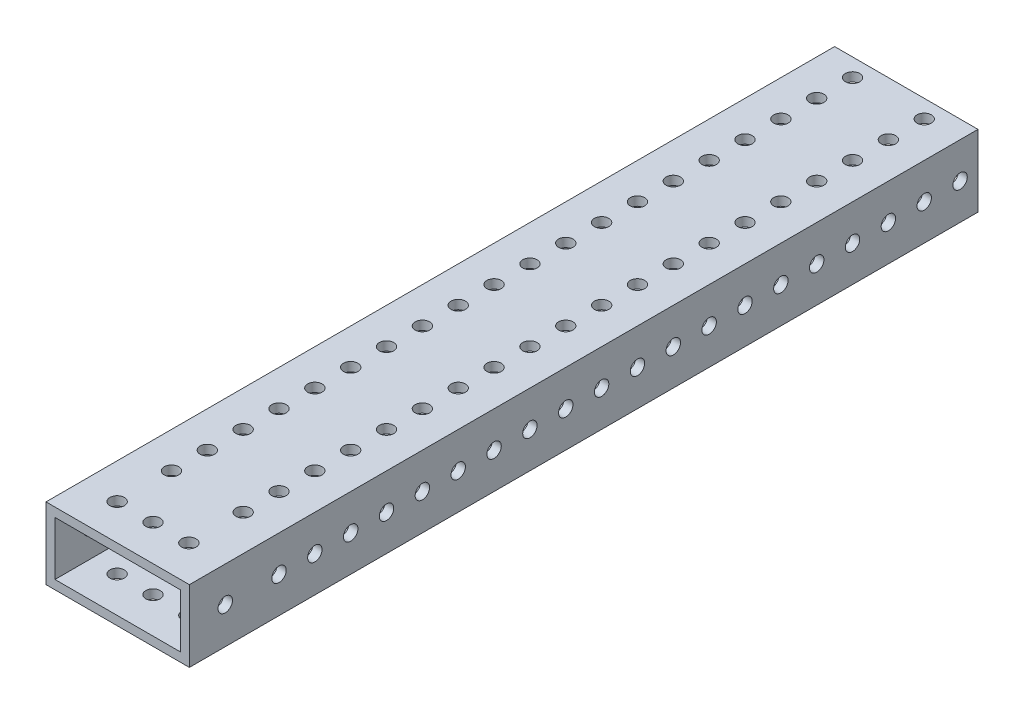
SolidWorks part; units mm, degrees
material "6061-T6 (SS)"
ref_plane "Front Plane" through (0, 0, 0) normal (0, 0, 1) x (1, 0, 0)
ref_plane "Top Plane" through (0, 0, 0) normal (0, 1, 0) x (1, 0, 0)
ref_plane "Right Plane" through (0, 0, 0) normal (1, 0, 0) x (0, 0, -1)
sketch "Sketch1" plane through (0, 0, 0) normal (0, 1, 0) x (1, 0, 0)
  line L1 (0, 0) -> (50.8, 0)
  line L2 (0, 0) -> (0, 279.4)
  line L3 (0, 279.4) -> (50.8, 279.4)
  line L4 (50.8, 0) -> (50.8, 279.4)
  dimension "D1" = 50.8
  dimension "D2" = 279.4
extrude "Boss-Extrude1" add sketch "Sketch1" along normal blind 25.4
sketch "Sketch2" plane through (0, 0, 0) normal (0, 0, 1) x (1, 0, 0)
  line L3 (3.175, 3.175) -> (47.625, 3.175)
  line L4 (3.175, 3.175) -> (3.175, 22.225)
  line L5 (3.175, 22.225) -> (47.625, 22.225)
  line L6 (47.625, 3.175) -> (47.625, 22.225)
  line L7 (0, 25.4) -> (0, 0) construction
  line L8 (50.8, 25.4) -> (50.8, 0) construction
  line L9 (0, 0) -> (50.8, 0) construction
  line L10 (0, 25.4) -> (50.8, 25.4) construction
  point P8 (25.4, 12.7)
  dimension "D1" = 3.175
  dimension "D2" = 3.175
  dimension "D3" = 3.175
  dimension "D4" = 3.175
extrude "Cut-Extrude1" cut sketch "Sketch2" against normal through all
sketch "Sketch4" plane through (0, 25.4, 0) normal (0, 1, 0) x (1, 0, 0)
  line L0 (0, 0) -> (50.8, 0) construction
  line L1 (0, 279.4) -> (0, 0) construction
  line L2 (50.8, 0) -> (50.8, 279.4) construction
  circle A0 centre (12.7, 6.35) radius 2.5527 construction
  circle A1 centre (38.1, 6.35) radius 2.5527 construction
  circle A2 centre (12.7, 19.05) radius 2.5527 construction
  circle A3 centre (38.1, 19.05) radius 2.5527 construction
  circle A4 centre (12.7, 31.75) radius 2.5527
  circle A5 centre (38.1, 31.75) radius 2.5527
  circle A6 centre (12.7, 44.45) radius 2.5527
  circle A7 centre (38.1, 44.45) radius 2.5527
  circle A8 centre (12.7, 57.15) radius 2.5527
  circle A9 centre (38.1, 57.15) radius 2.5527
  circle A10 centre (12.7, 69.85) radius 2.5527
  circle A11 centre (38.1, 69.85) radius 2.5527
  circle A12 centre (12.7, 82.55) radius 2.5527
  circle A13 centre (38.1, 82.55) radius 2.5527
  circle A14 centre (12.7, 95.25) radius 2.5527
  circle A15 centre (38.1, 95.25) radius 2.5527
  circle A16 centre (12.7, 107.95) radius 2.5527
  circle A17 centre (38.1, 107.95) radius 2.5527
  circle A18 centre (12.7, 120.65) radius 2.5527
  circle A19 centre (38.1, 120.65) radius 2.5527
  circle A20 centre (12.7, 133.35) radius 2.5527
  circle A21 centre (38.1, 133.35) radius 2.5527
  circle A22 centre (12.7, 146.05) radius 2.5527
  circle A23 centre (38.1, 146.05) radius 2.5527
  circle A24 centre (12.7, 158.75) radius 2.5527
  circle A25 centre (38.1, 158.75) radius 2.5527
  circle A26 centre (12.7, 171.45) radius 2.5527
  circle A27 centre (38.1, 171.45) radius 2.5527
  circle A28 centre (12.7, 184.15) radius 2.5527
  circle A29 centre (38.1, 184.15) radius 2.5527
  circle A30 centre (12.7, 196.85) radius 2.5527
  circle A31 centre (38.1, 196.85) radius 2.5527
  circle A32 centre (12.7, 209.55) radius 2.5527
  circle A33 centre (38.1, 209.55) radius 2.5527
  circle A34 centre (12.7, 222.25) radius 2.5527
  circle A35 centre (38.1, 222.25) radius 2.5527
  circle A36 centre (12.7, 234.95) radius 2.5527
  circle A37 centre (38.1, 234.95) radius 2.5527
  circle A38 centre (12.7, 247.65) radius 2.5527
  circle A39 centre (38.1, 247.65) radius 2.5527
  circle A40 centre (12.7, 260.35) radius 2.5527
  circle A41 centre (38.1, 260.35) radius 2.5527
  circle A42 centre (12.7, 273.05) radius 2.5527
  circle A43 centre (38.1, 273.05) radius 2.5527
  circle A44 centre (12.7, 285.75) radius 2.5527
  circle A45 centre (38.1, 285.75) radius 2.5527
  circle A46 centre (12.7, 298.45) radius 2.5527
  circle A47 centre (38.1, 298.45) radius 2.5527
  circle A48 centre (12.7, 311.15) radius 2.5527
  circle A49 centre (38.1, 311.15) radius 2.5527
  circle A50 centre (12.7, 323.85) radius 2.5527
  circle A51 centre (38.1, 323.85) radius 2.5527
  circle A52 centre (12.7, 336.55) radius 2.5527
  circle A53 centre (38.1, 336.55) radius 2.5527
  circle A54 centre (12.7, 349.25) radius 2.5527
  circle A55 centre (38.1, 349.25) radius 2.5527
  circle A56 centre (12.7, 361.95) radius 2.5527
  circle A57 centre (38.1, 361.95) radius 2.5527
  circle A58 centre (12.7, 374.65) radius 2.5527
  circle A59 centre (38.1, 374.65) radius 2.5527
  circle A60 centre (12.7, 387.35) radius 2.5527
  circle A61 centre (38.1, 387.35) radius 2.5527
  circle A62 centre (12.7, 400.05) radius 2.5527
  circle A63 centre (38.1, 400.05) radius 2.5527
  circle A64 centre (12.7, 412.75) radius 2.5527
  circle A65 centre (38.1, 412.75) radius 2.5527
  circle A66 centre (12.7, 425.45) radius 2.5527
  circle A67 centre (38.1, 425.45) radius 2.5527
  circle A68 centre (12.7, 438.15) radius 2.5527
  circle A69 centre (38.1, 438.15) radius 2.5527
  circle A70 centre (12.7, 450.85) radius 2.5527
  circle A71 centre (38.1, 450.85) radius 2.5527
  circle A72 centre (12.7, 463.55) radius 2.5527
  circle A73 centre (38.1, 463.55) radius 2.5527
  circle A74 centre (12.7, 476.25) radius 2.5527
  circle A75 centre (38.1, 476.25) radius 2.5527
  circle A76 centre (12.7, 488.95) radius 2.5527
  circle A77 centre (38.1, 488.95) radius 2.5527
  circle A78 centre (12.7, 501.65) radius 2.5527
  circle A79 centre (38.1, 501.65) radius 2.5527
  circle A81 centre (12.5095, 12.7) radius 2.5527
  circle A82 centre (25.2095, 12.7) radius 2.5527
  circle A84 centre (37.9095, 12.7) radius 2.5527
  dimension "D1" = 6.35
  dimension "D2" = 6.35
  dimension "D3" = 5.1054
  dimension "D4" = 5.1054
  dimension "D5" = 12.7
  dimension "D6" = 12.7
  dimension "D8" = 12.7
  dimension "D9" = 5.1054
  dimension "D10" = 12.5095
  dimension "D11" = 12.7
  dimension "D12" = 5.1054
  dimension "D13" = 12.7
  dimension "D14" = 12.7
  dimension "D15" = 12.7
  dimension "D16" = 5.1054
  dimension "D17" = 12.7
  dimension "D7" = 40
sketch "Sketch5" plane through (0, 0, 0) normal (-1, 0, 0) x (0, 0, 1)
  line L0 (-279.4, 0) -> (0, 0) construction
  line L1 (0, 25.4) -> (0, 0) construction
  line L3 (-116.3974, 0) -> (25.4, 0) construction
  line L4 (25.4, 76.2) -> (25.4, 0) construction
  circle A0 centre (-6.35, 12.7) radius 2.5527 construction
  circle A1 centre (-19.05, 12.7) radius 2.5527 construction
  circle A2 centre (-31.75, 12.7) radius 2.5527
  circle A3 centre (-44.45, 12.7) radius 2.5527
  circle A4 centre (-57.15, 12.7) radius 2.5527
  circle A5 centre (-69.85, 12.7) radius 2.5527
  circle A6 centre (-82.55, 12.7) radius 2.5527
  circle A7 centre (-95.25, 12.7) radius 2.5527
  circle A8 centre (-107.95, 12.7) radius 2.5527
  circle A9 centre (-120.65, 12.7) radius 2.5527
  circle A10 centre (-133.35, 12.7) radius 2.5527
  circle A11 centre (-146.05, 12.7) radius 2.5527
  circle A12 centre (-158.75, 12.7) radius 2.5527
  circle A13 centre (-171.45, 12.7) radius 2.5527
  circle A14 centre (-184.15, 12.7) radius 2.5527
  circle A15 centre (-196.85, 12.7) radius 2.5527
  circle A16 centre (-209.55, 12.7) radius 2.5527
  circle A17 centre (-222.25, 12.7) radius 2.5527
  circle A18 centre (-234.95, 12.7) radius 2.5527
  circle A19 centre (-247.65, 12.7) radius 2.5527
  circle A20 centre (-260.35, 12.7) radius 2.5527
  circle A21 centre (-273.05, 12.7) radius 2.5527
  circle A22 centre (-285.75, 12.7) radius 2.5527
  circle A23 centre (-298.45, 12.7) radius 2.5527
  circle A24 centre (-311.15, 12.7) radius 2.5527
  circle A25 centre (-323.85, 12.7) radius 2.5527
  circle A26 centre (-336.55, 12.7) radius 2.5527
  circle A27 centre (-349.25, 12.7) radius 2.5527
  circle A28 centre (-361.95, 12.7) radius 2.5527
  circle A29 centre (-374.65, 12.7) radius 2.5527
  circle A30 centre (-387.35, 12.7) radius 2.5527
  circle A31 centre (-400.05, 12.7) radius 2.5527
  circle A32 centre (-412.75, 12.7) radius 2.5527
  circle A33 centre (-425.45, 12.7) radius 2.5527
  circle A34 centre (-438.15, 12.7) radius 2.5527
  circle A35 centre (-450.85, 12.7) radius 2.5527
  circle A36 centre (-463.55, 12.7) radius 2.5527
  circle A37 centre (-476.25, 12.7) radius 2.5527
  circle A38 centre (-488.95, 12.7) radius 2.5527
  circle A39 centre (-501.65, 12.7) radius 2.5527
  circle A40 centre (-12.7, 12.954) radius 2.5527
  dimension "D1" = 12.7
  dimension "D2" = 6.35
  dimension "D3" = 5.1054
  dimension "D5" = 12.7
  dimension "D6" = 5.1054
  dimension "D7" = 12.954
  dimension "D8" = 38.1
  dimension "D4" = 40
extrude "Cut-Extrude2" cut sketch "Sketch4" against normal through all
extrude "Cut-Extrude3" cut sketch "Sketch5" against normal through all
